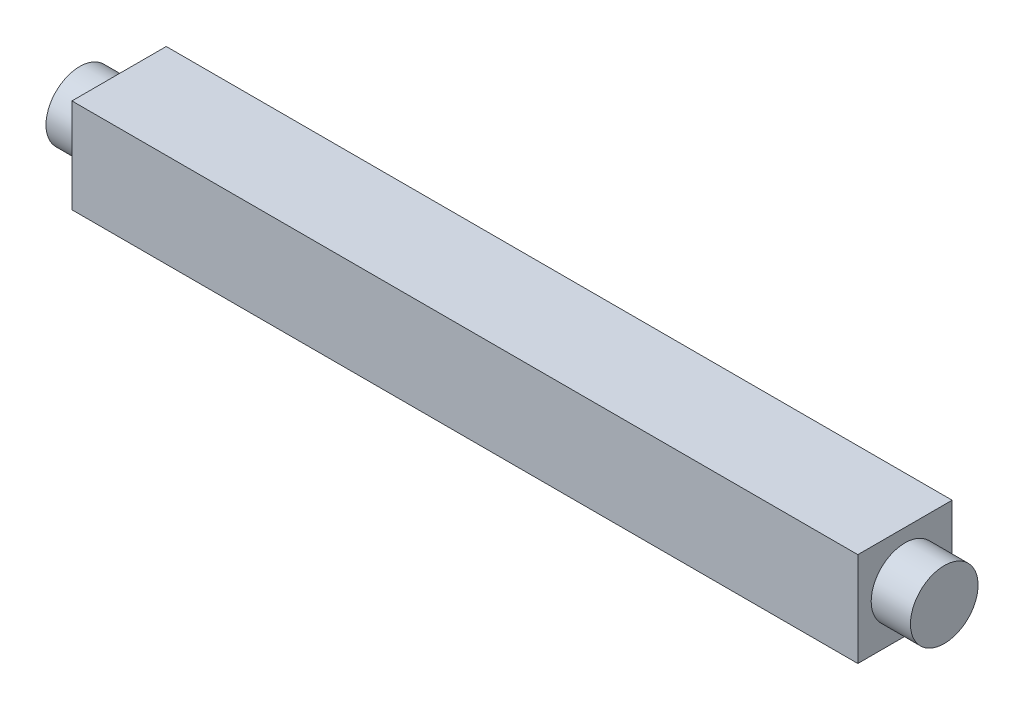
SolidWorks part; units mm, degrees
ref_plane "Front Plane" through (0, 0, 0) normal (0, 0, 1) x (1, 0, 0)
ref_plane "Top Plane" through (0, 0, 0) normal (0, 1, 0) x (1, 0, 0)
ref_plane "Right Plane" through (0, 0, 0) normal (1, 0, 0) x (0, 0, -1)
ref_axis "基準軸1" through (88.99, 0, 0) along (-1, 0, 0)
ref_axis "基準軸2" through (0, -55, 0) along (0, 1, 0)
ref_axis "基準軸3" through (0, 0, -88.99) along (0, 0, 1)
sketch "草圖1" plane through (0, 0, 0) normal (0, 0, 1) x (1, 0, 0)
  line L1 (0, 0) -> (50, 0)
  line L2 (0, 0) -> (0, 6)
  line L3 (0, 6) -> (50, 6)
  line L4 (50, 0) -> (50, 6)
  dimension "D1" = 50
  dimension "D2" = 6
extrude "填料-伸長1" add sketch "草圖1" along normal blind 6
sketch "草圖2" plane through (0, 0, 0) normal (-1, 0, 0) x (0, 0, 1)
  line L0 (0, -3.3) -> (0, 3.3) construction
  line L2 (3.3, 0) -> (-3.3, 0) construction
  circle A0 centre (3, 3) radius 2.15
  point P6 (4.5223, 0)
  dimension "D2" = 3
  dimension "D3" = 4.3
  dimension "D1" = 3
extrude "填料-伸長2" add sketch "草圖2" along normal blind 2.5
pattern_linear "直線複製排列1" count 2 spacing 52.5 along (1, 0, 0) of "填料-伸長2"
